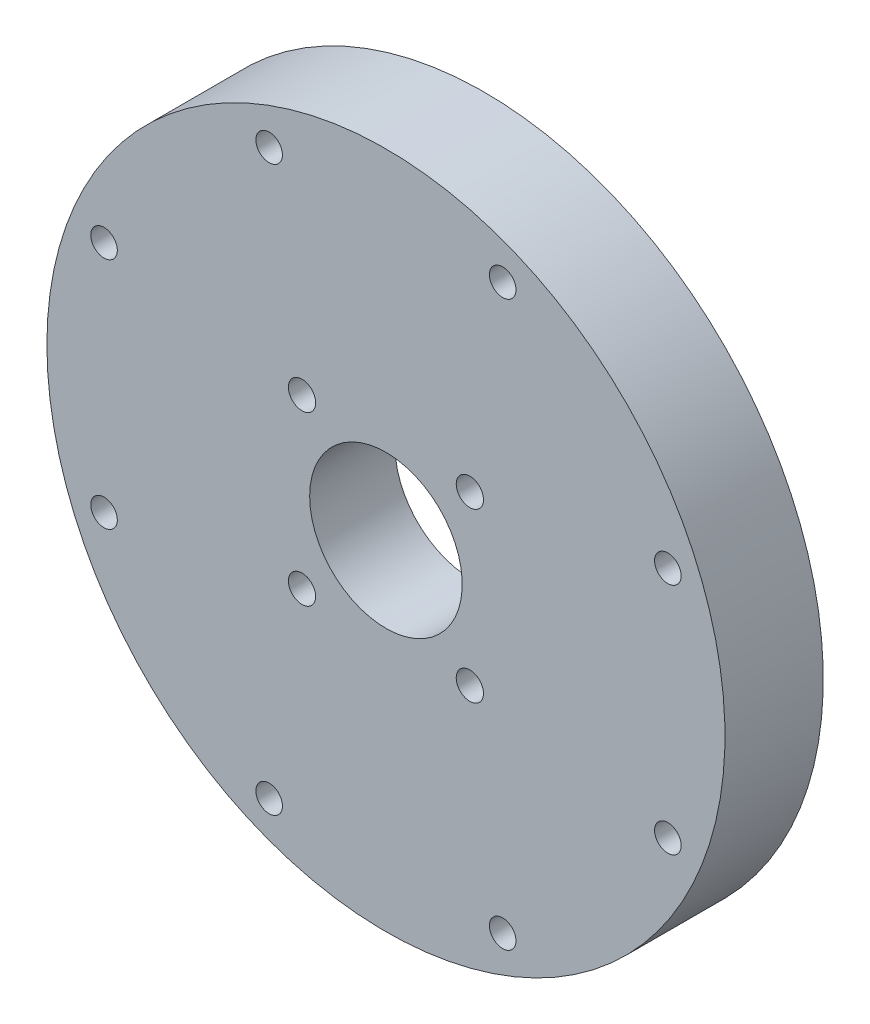
SolidWorks part; units mm, degrees
material "6061-T6 (SS)"
ref_plane "Front Plane" through (0, 0, 0) normal (0, 0, 1) x (1, 0, 0)
ref_plane "Top Plane" through (0, 0, 0) normal (0, 1, 0) x (1, 0, 0)
ref_plane "Right Plane" through (0, 0, 0) normal (1, 0, 0) x (0, 0, -1)
curve "Volute Curve"
  spline degree 3 poles (34.2618, 0, 0) (34.2648, 0.0718, 0) (34.2707, 0.2156, 0) (34.2778, 0.4312, 0) (34.2837, 0.647, 0) (34.2882, 0.8628, 0) (34.2914, 1.0787, 0) (34.2932, 1.2947, 0) (34.2937, 1.5108, 0) (34.2929, 1.7269, 0) (34.2907, 1.9431, 0) (34.2871, 2.1593, 0) (34.2822, 2.3756, 0) (34.2759, 2.5919, 0) (34.2683, 2.8082, 0) (34.2593, 3.0245, 0) (34.2489, 3.2407, 0) (34.2372, 3.457, 0) (34.2242, 3.6733, 0) (34.2098, 3.8895, 0) (34.194, 4.1058, 0) (34.1768, 4.3219, 0) (34.1583, 4.538, 0) (34.1385, 4.7541, 0) (34.1173, 4.9701, 0) (34.0947, 5.186, 0) (34.0708, 5.4018, 0) (34.0454, 5.6175, 0) (34.0188, 5.8331, 0) (33.9908, 6.0486, 0) (33.9614, 6.264, 0) (33.9306, 6.4793, 0) (33.8985, 6.6944, 0) (33.8651, 6.9094, 0) (33.8303, 7.1242, 0) (33.7941, 7.3388, 0) (33.7566, 7.5533, 0) (33.7177, 7.7676, 0) (33.6774, 7.9817, 0) (33.6358, 8.1956, 0) (33.5929, 8.4093, 0) (33.5486, 8.6228, 0) (33.5029, 8.8361, 0) (33.4559, 9.0491, 0) (33.4076, 9.2619, 0) (33.3579, 9.4745, 0) (33.3068, 9.6868, 0) (33.2544, 9.8988, 0) (33.2006, 10.1105, 0) (33.1456, 10.322, 0) (33.0891, 10.5332, 0) (33.0313, 10.744, 0) (32.9722, 10.9546, 0) (32.9118, 11.1648, 0) (32.85, 11.3748, 0) (32.7869, 11.5843, 0) (32.7224, 11.7936, 0) (32.6566, 12.0025, 0) (32.5895, 12.211, 0) (32.521, 12.4192, 0) (32.4513, 12.627, 0) (32.3802, 12.8344, 0) (32.3077, 13.0414, 0) (32.234, 13.248, 0) (32.1589, 13.4542, 0) (32.0826, 13.6599, 0) (32.0049, 13.8653, 0) (31.9259, 14.0702, 0) (31.8456, 14.2747, 0) (31.764, 14.4787, 0) (31.6811, 14.6823, 0) (31.5968, 14.8854, 0) (31.5113, 15.088, 0) (31.4245, 15.2901, 0) (31.3364, 15.4917, 0) (31.247, 15.6929, 0) (31.1563, 15.8935, 0) (31.0644, 16.0936, 0) (30.9711, 16.2932, 0) (30.8766, 16.4922, 0) (30.7808, 16.6907, 0) (30.6837, 16.8886, 0) (30.5854, 17.086, 0) (30.4858, 17.2829, 0) (30.3849, 17.4791, 0) (30.2828, 17.6748, 0) (30.1794, 17.8698, 0) (30.0747, 18.0643, 0) (29.9688, 18.2582, 0) (29.8617, 18.4514, 0) (29.7533, 18.644, 0) (29.6437, 18.836, 0) (29.5328, 19.0274, 0) (29.4208, 19.2181, 0) (29.3074, 19.4081, 0) (29.1929, 19.5975, 0) (29.0771, 19.7862, 0) (28.9601, 19.9742, 0) (28.842, 20.1616, 0) (28.7226, 20.3482, 0) (28.602, 20.5342, 0) (28.4801, 20.7194, 0) (28.3571, 20.904, 0) (28.233, 21.0877, 0) (28.1076, 21.2708, 0) (27.981, 21.4531, 0) (27.8533, 21.6347, 0) (27.7243, 21.8155, 0) (27.5942, 21.9956, 0) (27.463, 22.1748, 0) (27.3306, 22.3533, 0) (27.197, 22.531, 0) (27.0623, 22.708, 0) (26.9264, 22.8841, 0) (26.7894, 23.0594, 0) (26.6512, 23.2339, 0) (26.5119, 23.4075, 0) (26.3715, 23.5804, 0) (26.23, 23.7524, 0) (26.0873, 23.9235, 0) (25.9435, 24.0938, 0) (25.7987, 24.2632, 0) (25.6527, 24.4318, 0) (25.5056, 24.5995, 0) (25.3574, 24.7663, 0) (25.2082, 24.9322, 0) (25.0578, 25.0973, 0) (24.9064, 25.2614, 0) (24.7539, 25.4246, 0) (24.6003, 25.5869, 0) (24.4457, 25.7483, 0) (24.29, 25.9087, 0) (24.1333, 26.0682, 0) (23.9755, 26.2268, 0) (23.8167, 26.3844, 0) (23.6569, 26.541, 0) (23.496, 26.6967, 0) (23.3341, 26.8514, 0) (23.1712, 27.0051, 0) (23.0073, 27.1579, 0) (22.8424, 27.3096, 0) (22.6765, 27.4604, 0) (22.5096, 27.6101, 0) (22.3417, 27.7589, 0) (22.1728, 27.9066, 0) (22.003, 28.0533, 0) (21.8322, 28.199, 0) (21.6604, 28.3436, 0) (21.4877, 28.4872, 0) (21.314, 28.6297, 0) (21.1394, 28.7712, 0) (20.9639, 28.9116, 0) (20.7874, 29.051, 0) (20.61, 29.1892, 0) (20.4317, 29.3264, 0) (20.2524, 29.4626, 0) (20.0723, 29.5976, 0) (19.8913, 29.7315, 0) (19.7094, 29.8643, 0) (19.5266, 29.996, 0) (19.3429, 30.1266, 0) (19.1584, 30.2561, 0) (18.973, 30.3844, 0) (18.7867, 30.5116, 0) (18.5996, 30.6377, 0) (18.4117, 30.7626, 0) (18.2229, 30.8864, 0) (18.0333, 31.009, 0) (17.8429, 31.1304, 0) (17.6516, 31.2507, 0) (17.4596, 31.3698, 0) (17.2667, 31.4878, 0) (17.0731, 31.6045, 0) (16.8786, 31.7201, 0) (16.6834, 31.8344, 0) (16.4875, 31.9476, 0) (16.2907, 32.0596, 0) (16.0932, 32.1703, 0) (15.895, 32.2799, 0) (15.696, 32.3882, 0) (15.4963, 32.4953, 0) (15.2959, 32.6012, 0) (15.0947, 32.7058, 0) (14.8929, 32.8092, 0) (14.6903, 32.9114, 0) (14.487, 33.0123, 0) (14.2831, 33.1119, 0) (14.0784, 33.2103, 0) (13.8731, 33.3075, 0) (13.6672, 33.4033, 0) (13.4606, 33.4979, 0) (13.2533, 33.5912, 0) (13.0454, 33.6833, 0) (12.8368, 33.774, 0) (12.6277, 33.8635, 0) (12.4179, 33.9517, 0) (12.2075, 34.0385, 0) (11.9965, 34.1241, 0) (11.7849, 34.2084, 0) (11.5727, 34.2913, 0) (11.36, 34.373, 0) (11.1467, 34.4533, 0) (10.9328, 34.5323, 0) (10.7183, 34.61, 0) (10.5034, 34.6863, 0) (10.2879, 34.7613, 0) (10.0718, 34.835, 0) (9.8553, 34.9074, 0) (9.6382, 34.9783, 0) (9.4206, 35.048, 0) (9.2025, 35.1163, 0) (8.984, 35.1832, 0) (8.765, 35.2488, 0) (8.5455, 35.313, 0) (8.3255, 35.3759, 0) (8.1051, 35.4374, 0) (7.8842, 35.4975, 0) (7.6629, 35.5562, 0) (7.4412, 35.6136, 0) (7.2191, 35.6696, 0) (6.9965, 35.7242, 0) (6.7736, 35.7774, 0) (6.5503, 35.8292, 0) (6.3265, 35.8796, 0) (6.1024, 35.9287, 0) (5.878, 35.9763, 0) (5.6532, 36.0225, 0) (5.428, 36.0674, 0) (5.2025, 36.1108, 0) (4.9766, 36.1528, 0) (4.7505, 36.1934, 0) (4.524, 36.2326, 0) (4.2972, 36.2704, 0) (4.0701, 36.3067, 0) (3.8428, 36.3417, 0) (3.6151, 36.3752, 0) (3.3872, 36.4073, 0) (3.159, 36.438, 0) (2.9306, 36.4672, 0) (2.7019, 36.495, 0) (2.473, 36.5214, 0) (2.2439, 36.5463, 0) (2.0146, 36.5699, 0) (1.785, 36.5919, 0) (1.5553, 36.6126, 0) (1.3253, 36.6318, 0) (1.0952, 36.6495, 0) (0.8649, 36.6658, 0) (0.6345, 36.6807, 0) (0.4039, 36.6941, 0) (0.1731, 36.706, 0) (-0.0577, 36.7166, 0) (-0.2887, 36.7256, 0) (-0.5199, 36.7332, 0) (-0.7511, 36.7394, 0) (-0.9824, 36.7441, 0) (-1.2138, 36.7474, 0) (-1.4453, 36.7492, 0) (-1.6769, 36.7495, 0) (-1.9085, 36.7484, 0) (-2.1402, 36.7458, 0) (-2.3719, 36.7418, 0) (-2.6037, 36.7363, 0) (-2.8355, 36.7293, 0) (-3.0673, 36.7209, 0) (-3.2991, 36.711, 0) (-3.5309, 36.6997, 0) (-3.7627, 36.6869, 0) (-3.9944, 36.6726, 0) (-4.2262, 36.6569, 0) (-4.4579, 36.6397, 0) (-4.6895, 36.6211, 0) (-4.9211, 36.6009, 0) (-5.1526, 36.5794, 0) (-5.3841, 36.5563, 0) (-5.6154, 36.5318, 0) (-5.8467, 36.5059, 0) (-6.0779, 36.4784, 0) (-6.3089, 36.4495, 0) (-6.5399, 36.4192, 0) (-6.7706, 36.3874, 0) (-7.0013, 36.3541, 0) (-7.2318, 36.3194, 0) (-7.4621, 36.2832, 0) (-7.6923, 36.2455, 0) (-7.9223, 36.2064, 0) (-8.1521, 36.1658, 0) (-8.3817, 36.1238, 0) (-8.6111, 36.0803, 0) (-8.8403, 36.0354, 0) (-9.0693, 35.989, 0) (-9.298, 35.9411, 0) (-9.5265, 35.8918, 0) (-9.7548, 35.8411, 0) (-9.9827, 35.7889, 0) (-10.2105, 35.7352, 0) (-10.4379, 35.6802, 0) (-10.665, 35.6236, 0) (-10.8919, 35.5656, 0) (-11.1184, 35.5062, 0) (-11.3446, 35.4453, 0) (-11.5705, 35.383, 0) (-11.7961, 35.3193, 0) (-12.0213, 35.2541, 0) (-12.2461, 35.1875, 0) (-12.4706, 35.1194, 0) (-12.6948, 35.0499, 0) (-12.9185, 34.979, 0) (-13.1419, 34.9067, 0) (-13.3648, 34.8329, 0) (-13.5874, 34.7578, 0) (-13.8095, 34.6812, 0) (-14.0312, 34.6031, 0) (-14.2525, 34.5237, 0) (-14.4734, 34.4429, 0) (-14.6937, 34.3606, 0) (-14.9137, 34.2769, 0) (-15.1331, 34.1918, 0) (-15.3521, 34.1054, 0) (-15.5706, 34.0175, 0) (-15.7885, 33.9282, 0) (-16.006, 33.8375, 0) (-16.223, 33.7455, 0) (-16.4394, 33.652, 0) (-16.6553, 33.5572, 0) (-16.8707, 33.461, 0) (-17.0855, 33.3634, 0) (-17.2997, 33.2644, 0) (-17.5134, 33.164, 0) (-17.7265, 33.0623, 0) (-17.939, 32.9592, 0) (-18.151, 32.8548, 0) (-18.3623, 32.7489, 0) (-18.573, 32.6418, 0) (-18.7831, 32.5332, 0) (-18.9925, 32.4234, 0) (-19.2014, 32.3121, 0) (-19.4095, 32.1996, 0) (-19.6171, 32.0857, 0) (-19.8239, 31.9704, 0) (-20.0301, 31.8538, 0) (-20.2356, 31.7359, 0) (-20.4404, 31.6167, 0) (-20.6445, 31.4962, 0) (-20.8479, 31.3743, 0) (-21.0506, 31.2511, 0) (-21.2526, 31.1267, 0) (-21.4538, 31.0009, 0) (-21.6543, 30.8738, 0) (-21.854, 30.7454, 0) (-22.053, 30.6158, 0) (-22.2512, 30.4848, 0) (-22.4487, 30.3526, 0) (-22.6453, 30.2191, 0) (-22.8412, 30.0843, 0) (-23.0363, 29.9482, 0) (-23.2305, 29.8109, 0) (-23.424, 29.6723, 0) (-23.6166, 29.5325, 0) (-23.8084, 29.3915, 0) (-23.9994, 29.2491, 0) (-24.1895, 29.1056, 0) (-24.3787, 28.9608, 0) (-24.5671, 28.8148, 0) (-24.7546, 28.6676, 0) (-24.9413, 28.5191, 0) (-25.127, 28.3694, 0) (-25.3119, 28.2186, 0) (-25.4958, 28.0665, 0) (-25.6789, 27.9132, 0) (-25.861, 27.7587, 0) (-26.0422, 27.6031, 0) (-26.2224, 27.4463, 0) (-26.4018, 27.2882, 0) (-26.5801, 27.1291, 0) (-26.7576, 26.9687, 0) (-26.934, 26.8072, 0) (-27.1095, 26.6446, 0) (-27.284, 26.4808, 0) (-27.4575, 26.3159, 0) (-27.63, 26.1498, 0) (-27.8015, 25.9826, 0) (-27.972, 25.8143, 0) (-28.1415, 25.6448, 0) (-28.31, 25.4743, 0) (-28.4774, 25.3027, 0) (-28.6438, 25.1299, 0) (-28.8092, 24.9561, 0) (-28.9735, 24.7811, 0) (-29.1367, 24.6051, 0) (-29.2989, 24.4281, 0) (-29.46, 24.2499, 0) (-29.62, 24.0707, 0) (-29.7789, 23.8905, 0) (-29.9368, 23.7092, 0) (-30.0935, 23.5268, 0) (-30.2491, 23.3435, 0) (-30.4036, 23.1591, 0) (-30.557, 22.9737, 0) (-30.7093, 22.7872, 0) (-30.8604, 22.5998, 0) (-31.0104, 22.4114, 0) (-31.1592, 22.2219, 0) (-31.3069, 22.0315, 0) (-31.4534, 21.8402, 0) (-31.5988, 21.6478, 0) (-31.7429, 21.4545, 0) (-31.8859, 21.2602, 0) (-32.0277, 21.065, 0) (-32.1684, 20.8688, 0) (-32.3078, 20.6717, 0) (-32.446, 20.4737, 0) (-32.583, 20.2747, 0) (-32.7188, 20.0748, 0) (-32.8533, 19.8741, 0) (-32.9866, 19.6724, 0) (-33.1187, 19.4698, 0) (-33.2496, 19.2664, 0) (-33.3792, 19.0621, 0) (-33.5075, 18.8569, 0) (-33.6346, 18.6509, 0) (-33.7604, 18.444, 0) (-33.885, 18.2362, 0) (-34.0082, 18.0276, 0) (-34.1302, 17.8182, 0) (-34.2509, 17.608, 0) (-34.3703, 17.397, 0) (-34.4884, 17.1851, 0) (-34.6052, 16.9725, 0) (-34.7207, 16.7591, 0) (-34.8349, 16.5449, 0) (-34.9478, 16.3299, 0) (-35.0593, 16.1141, 0) (-35.1695, 15.8976, 0) (-35.2784, 15.6804, 0) (-35.3859, 15.4624, 0) (-35.4921, 15.2436, 0) (-35.597, 15.0242, 0) (-35.7004, 14.804, 0) (-35.8026, 14.5832, 0) (-35.9033, 14.3616, 0) (-36.0027, 14.1393, 0) (-36.1007, 13.9164, 0) (-36.1973, 13.6928, 0) (-36.2926, 13.4685, 0) (-36.3864, 13.2436, 0) (-36.4789, 13.018, 0) (-36.57, 12.7918, 0) (-36.6596, 12.5649, 0) (-36.7479, 12.3374, 0) (-36.8348, 12.1094, 0) (-36.9202, 11.8807, 0) (-37.0042, 11.6514, 0) (-37.0868, 11.4215, 0) (-37.168, 11.1911, 0) (-37.2477, 10.96, 0) (-37.326, 10.7285, 0) (-37.4029, 10.4963, 0) (-37.4783, 10.2637, 0) (-37.5523, 10.0305, 0) (-37.6248, 9.7967, 0) (-37.6959, 9.5625, 0) (-37.7655, 9.3277, 0) (-37.8337, 9.0925, 0) (-37.9004, 8.8568, 0) (-37.9656, 8.6205, 0) (-38.0293, 8.3839, 0) (-38.0916, 8.1467, 0) (-38.1524, 7.9091, 0) (-38.2117, 7.6711, 0) (-38.2696, 7.4326, 0) (-38.3259, 7.1937, 0) (-38.3808, 6.9544, 0) (-38.4342, 6.7147, 0) (-38.486, 6.4746, 0) (-38.5364, 6.2341, 0) (-38.5853, 5.9932, 0) (-38.6326, 5.7519, 0) (-38.6785, 5.5103, 0) (-38.7229, 5.2684, 0) (-38.7657, 5.0261, 0) (-38.807, 4.7835, 0) (-38.8468, 4.5405, 0) (-38.8851, 4.2973, 0) (-38.9219, 4.0537, 0) (-38.9571, 3.8099, 0) (-38.9908, 3.5657, 0) (-39.023, 3.3213, 0) (-39.0537, 3.0767, 0) (-39.0828, 2.8317, 0) (-39.1104, 2.5866, 0) (-39.1364, 2.3412, 0) (-39.1609, 2.0955, 0) (-39.1839, 1.8497, 0) (-39.2053, 1.6037, 0) (-39.2252, 1.3574, 0) (-39.2435, 1.111, 0) (-39.2603, 0.8644, 0) (-39.2756, 0.6176, 0) (-39.2893, 0.3707, 0) (-39.3014, 0.1236, 0) (-39.312, -0.1236, 0) (-39.321, -0.371, 0) (-39.3285, -0.6185, 0) (-39.3344, -0.866, 0) (-39.3388, -1.1137, 0) (-39.3416, -1.3615, 0) (-39.3428, -1.6093, 0) (-39.3425, -1.8572, 0) (-39.3406, -2.1052, 0) (-39.3372, -2.3532, 0) (-39.3322, -2.6013, 0) (-39.3257, -2.8494, 0) (-39.3175, -3.0975, 0) (-39.3078, -3.3456, 0) (-39.2966, -3.5937, 0) (-39.2838, -3.8418, 0) (-39.2694, -4.0899, 0) (-39.2534, -4.338, 0) (-39.2359, -4.586, 0) (-39.2168, -4.834, 0) (-39.1962, -5.0819, 0) (-39.174, -5.3298, 0) (-39.1502, -5.5776, 0) (-39.1248, -5.8252, 0) (-39.0979, -6.0728, 0) (-39.0694, -6.3203, 0) (-39.0394, -6.5677, 0) (-39.0078, -6.8149, 0) (-38.9746, -7.062, 0) (-38.9399, -7.309, 0) (-38.9036, -7.5558, 0) (-38.8657, -7.8024, 0) (-38.8263, -8.0488, 0) (-38.7853, -8.2951, 0) (-38.7427, -8.5411, 0) (-38.6986, -8.787, 0) (-38.653, -9.0326, 0) (-38.6057, -9.2781, 0) (-38.557, -9.5232, 0) (-38.5066, -9.7682, 0) (-38.4547, -10.0128, 0) (-38.4013, -10.2572, 0) (-38.3463, -10.5014, 0) (-38.2897, -10.7452, 0) (-38.2316, -10.9888, 0) (-38.172, -11.232, 0) (-38.1108, -11.475, 0) (-38.048, -11.7176, 0) (-37.9838, -11.9598, 0) (-37.9179, -12.2018, 0) (-37.8506, -12.4433, 0) (-37.7817, -12.6845, 0) (-37.7112, -12.9254, 0) (-37.6393, -13.1658, 0) (-37.5658, -13.4059, 0) (-37.4907, -13.6455, 0) (-37.4142, -13.8848, 0) (-37.3361, -14.1236, 0) (-37.2565, -14.362, 0) (-37.1753, -14.5999, 0) (-37.0927, -14.8374, 0) (-37.0085, -15.0744, 0) (-36.9228, -15.311, 0) (-36.8357, -15.547, 0) (-36.747, -15.7826, 0) (-36.6568, -16.0177, 0) (-36.5651, -16.2523, 0) (-36.4719, -16.4863, 0) (-36.3772, -16.7199, 0) (-36.281, -16.9528, 0) (-36.1833, -17.1853, 0) (-36.0841, -17.4172, 0) (-35.9834, -17.6485, 0) (-35.8813, -17.8792, 0) (-35.7777, -18.1094, 0) (-35.6726, -18.3389, 0) (-35.566, -18.5679, 0) (-35.458, -18.7962, 0) (-35.3485, -19.0239, 0) (-35.2376, -19.251, 0) (-35.1251, -19.4774, 0) (-35.0113, -19.7032, 0) (-34.896, -19.9283, 0) (-34.7792, -20.1528, 0) (-34.661, -20.3765, 0) (-34.5414, -20.5996, 0) (-34.4203, -20.822, 0) (-34.2978, -21.0437, 0) (-34.1738, -21.2646, 0) (-34.0485, -21.4849, 0) (-33.9217, -21.7044, 0) (-33.7935, -21.9231, 0) (-33.6639, -22.1411, 0) (-33.5329, -22.3584, 0) (-33.4005, -22.5748, 0) (-33.2667, -22.7905, 0) (-33.1315, -23.0054, 0) (-32.995, -23.2195, 0) (-32.857, -23.4328, 0) (-32.7177, -23.6453, 0) (-32.577, -23.8569, 0) (-32.4349, -24.0677, 0) (-32.2915, -24.2777, 0) (-32.1467, -24.4868, 0) (-32.0006, -24.6951, 0) (-31.8531, -24.9025, 0) (-31.7042, -25.109, 0) (-31.5541, -25.3146, 0) (-31.4026, -25.5194, 0) (-31.2497, -25.7232, 0) (-31.0956, -25.9261, 0) (-30.9401, -26.1281, 0) (-30.7833, -26.3292, 0) (-30.6253, -26.5293, 0) (-30.4659, -26.7285, 0) (-30.3052, -26.9267, 0) (-30.1433, -27.124, 0) (-29.98, -27.3203, 0) (-29.8155, -27.5156, 0) (-29.6497, -27.7099, 0) (-29.4827, -27.9032, 0) (-29.3144, -28.0956, 0) (-29.1448, -28.2869, 0) (-28.974, -28.4772, 0) (-28.8019, -28.6664, 0) (-28.6287, -28.8546, 0) (-28.4542, -29.0418, 0) (-28.2784, -29.2279, 0) (-28.1015, -29.413, 0) (-27.9233, -29.597, 0) (-27.744, -29.7799, 0) (-27.5634, -29.9618, 0) (-27.3817, -30.1425, 0) (-27.1987, -30.3221, 0) (-27.0146, -30.5007, 0) (-26.8294, -30.6781, 0) (-26.6429, -30.8544, 0) (-26.4554, -31.0296, 0) (-26.2666, -31.2036, 0) (-26.0767, -31.3765, 0) (-25.8857, -31.5482, 0) (-25.6936, -31.7188, 0) (-25.5003, -31.8882, 0) (-25.306, -32.0564, 0) (-25.1105, -32.2234, 0) (-24.9139, -32.3893, 0) (-24.7162, -32.5539, 0) (-24.5175, -32.7174, 0) (-24.3176, -32.8796, 0) (-24.1167, -33.0406, 0) (-23.9147, -33.2004, 0) (-23.7117, -33.359, 0) (-23.5076, -33.5163, 0) (-23.3025, -33.6724, 0) (-23.0964, -33.8272, 0) (-22.8892, -33.9807, 0) (-22.681, -34.133, 0) (-22.4718, -34.2841, 0) (-22.2616, -34.4338, 0) (-22.0504, -34.5822, 0) (-21.8382, -34.7294, 0) (-21.6251, -34.8752, 0) (-21.4109, -35.0198, 0) (-21.1959, -35.163, 0) (-20.9798, -35.3049, 0) (-20.7628, -35.4455, 0) (-20.5449, -35.5848, 0) (-20.326, -35.7227, 0) (-20.1062, -35.8593, 0) (-19.8855, -35.9945, 0) (-19.6639, -36.1284, 0) (-19.4414, -36.2609, 0) (-19.2181, -36.392, 0) (-18.9938, -36.5218, 0) (-18.7686, -36.6502, 0) (-18.5426, -36.7772, 0) (-18.3158, -36.9028, 0) (-18.0881, -37.027, 0) (-17.8595, -37.1498, 0) (-17.6302, -37.2712, 0) (-17.4, -37.3911, 0) (-17.169, -37.5097, 0) (-16.9372, -37.6268, 0) (-16.7046, -37.7425, 0) (-16.4712, -37.8568, 0) (-16.237, -37.9696, 0) (-16.0021, -38.081, 0) (-15.7664, -38.1909, 0) (-15.53, -38.2994, 0) (-15.2928, -38.4064, 0) (-15.0549, -38.5119, 0) (-14.8163, -38.616, 0) (-14.577, -38.7185, 0) (-14.3369, -38.8196, 0) (-14.0962, -38.9192, 0) (-13.8547, -39.0174, 0) (-13.6126, -39.114, 0) (-13.3699, -39.2091, 0) (-13.1265, -39.3027, 0) (-12.8824, -39.3949, 0) (-12.6377, -39.4854, 0) (-12.3923, -39.5745, 0) (-12.1464, -39.6621, 0) (-11.8998, -39.7481, 0) (-11.6526, -39.8326, 0) (-11.4048, -39.9155, 0) (-11.1565, -39.997, 0) (-10.9076, -40.0768, 0) (-10.6581, -40.1552, 0) (-10.408, -40.2319, 0) (-10.1575, -40.3071, 0) (-9.9063, -40.3808, 0) (-9.6547, -40.4529, 0) (-9.4025, -40.5234, 0) (-9.1499, -40.5924, 0) (-8.8967, -40.6598, 0) (-8.6431, -40.7256, 0) (-8.389, -40.7898, 0) (-8.1344, -40.8524, 0) (-7.8793, -40.9135, 0) (-7.6239, -40.9729, 0) (-7.3679, -41.0308, 0) (-7.1116, -41.087, 0) (-6.8548, -41.1417, 0) (-6.5977, -41.1948, 0) (-6.3401, -41.2462, 0) (-6.0821, -41.2961, 0) (-5.8238, -41.3443, 0) (-5.5651, -41.3909, 0) (-5.3061, -41.4359, 0) (-5.0467, -41.4793, 0) (-4.7869, -41.5211, 0) (-4.5269, -41.5612, 0) (-4.2665, -41.5997, 0) (-4.0058, -41.6366, 0) (-3.7449, -41.6718, 0) (-3.4836, -41.7054, 0) (-3.2221, -41.7374, 0) (-2.9603, -41.7677, 0) (-2.6982, -41.7964, 0) (-2.4359, -41.8234, 0) (-2.1734, -41.8488, 0) (-1.9106, -41.8726, 0) (-1.6477, -41.8947, 0) (-1.3845, -41.9151, 0) (-1.1212, -41.9339, 0) (-0.8576, -41.9511, 0) (-0.5939, -41.9666, 0) (-0.33, -41.9804, 0) (-0.066, -41.9926, 0) (0.1981, -42.0031, 0) (0.4624, -42.012, 0) (0.7268, -42.0192, 0) (0.9914, -42.0247, 0) (1.256, -42.0286, 0) (1.5207, -42.0308, 0) (1.7855, -42.0313, 0) (2.0503, -42.0302, 0) (2.3152, -42.0274, 0) (2.5802, -42.0229, 0) (2.8452, -42.0168, 0) (3.1102, -42.0089, 0) (3.3752, -41.9995, 0) (3.6403, -41.9883, 0) (3.9053, -41.9755, 0) (4.1703, -41.961, 0) (4.4353, -41.9448, 0) (4.7002, -41.927, 0) (4.9651, -41.9075, 0) (5.2299, -41.8863, 0) (5.4947, -41.8634, 0) (5.7594, -41.8389, 0) (6.024, -41.8127, 0) (6.2885, -41.7848, 0) (6.5528, -41.7553, 0) (6.8171, -41.7241, 0) (7.0812, -41.6912, 0) (7.3452, -41.6566, 0) (7.609, -41.6204, 0) (7.8727, -41.5825, 0) (8.1362, -41.5429, 0) (8.3995, -41.5017, 0) (8.6626, -41.4588, 0) (8.9254, -41.4142, 0) (9.1881, -41.3679, 0) (9.4506, -41.32, 0) (9.7128, -41.2705, 0) (9.9747, -41.2192, 0) (10.2364, -41.1663, 0) (10.4979, -41.1118, 0) (10.759, -41.0556, 0) (11.0199, -40.9977, 0) (11.2804, -40.9382, 0) (11.5407, -40.877, 0) (11.8006, -40.8141, 0) (12.0602, -40.7496, 0) (12.3194, -40.6835, 0) (12.5783, -40.6157, 0) (12.8368, -40.5463, 0) (13.0949, -40.4752, 0) (13.3527, -40.4025, 0) (13.6101, -40.3281, 0) (13.867, -40.2521, 0) (14.1235, -40.1745, 0) (14.3797, -40.0952, 0) (14.6353, -40.0143, 0) (14.8905, -39.9318, 0) (15.1453, -39.8476, 0) (15.3996, -39.7618, 0) (15.6534, -39.6744, 0) (15.9067, -39.5854, 0) (16.1596, -39.4948, 0) (16.4119, -39.4025, 0) (16.6637, -39.3087, 0) (16.9149, -39.2132, 0) (17.1657, -39.1161, 0) (17.4158, -39.0174, 0) (17.6654, -38.9172, 0) (17.9145, -38.8153, 0) (18.1629, -38.7118, 0) (18.4108, -38.6068, 0) (18.658, -38.5001, 0) (18.9047, -38.3919, 0) (19.1507, -38.2821, 0) (19.3961, -38.1707, 0) (19.6408, -38.0578, 0) (19.8849, -37.9433, 0) (20.1283, -37.8272, 0) (20.3711, -37.7095, 0) (20.6132, -37.5904, 0) (20.8546, -37.4696, 0) (21.0952, -37.3473, 0) (21.3352, -37.2235, 0) (21.5744, -37.0981, 0) (21.8129, -36.9712, 0) (22.0507, -36.8427, 0) (22.2877, -36.7127, 0) (22.524, -36.5812, 0) (22.7594, -36.4482, 0) (22.9941, -36.3137, 0) (23.228, -36.1776, 0) (23.4611, -36.0401, 0) (23.6934, -35.901, 0) (23.9249, -35.7605, 0) (24.1556, -35.6184, 0) (24.3854, -35.4749, 0) (24.6143, -35.3299, 0) (24.8424, -35.1834, 0) (25.0696, -35.0355, 0) (25.296, -34.8861, 0) (25.5214, -34.7352, 0) (25.746, -34.5828, 0) (25.9696, -34.4291, 0) (26.1924, -34.2738, 0) (26.4142, -34.1172, 0) (26.6351, -33.9591, 0) (26.855, -33.7995, 0) (27.074, -33.6386, 0) (27.292, -33.4762, 0) (27.5091, -33.3124, 0) (27.7252, -33.1472, 0) (27.9402, -32.9807, 0) (28.1543, -32.8127, 0) (28.3674, -32.6433, 0) (28.5795, -32.4726, 0) (28.7905, -32.3004, 0) (29.0005, -32.127, 0) (29.2095, -31.9521, 0) (29.4174, -31.7759, 0) (29.6242, -31.5983, 0) (29.83, -31.4194, 0) (30.0347, -31.2392, 0) (30.2383, -31.0576, 0) (30.4408, -30.8747, 0) (30.6422, -30.6905, 0) (30.8426, -30.5049, 0) (31.0417, -30.3181, 0) (31.2398, -30.1299, 0) (31.4367, -29.9405, 0) (31.6325, -29.7498, 0) (31.8271, -29.5578, 0) (32.0205, -29.3645, 0) (32.2128, -29.17, 0) (32.4039, -28.9742, 0) (32.5938, -28.7772, 0) (32.7825, -28.5789, 0) (32.97, -28.3794, 0) (33.1563, -28.1787, 0) (33.3414, -27.9767, 0) (33.5252, -27.7736, 0) (33.7079, -27.5692, 0) (33.8892, -27.3636, 0) (34.0693, -27.1569, 0) (34.2482, -26.9489, 0) (34.4258, -26.7398, 0) (34.6021, -26.5295, 0) (34.7771, -26.3181, 0) (34.9509, -26.1055, 0) (35.1233, -25.8917, 0) (35.2944, -25.6768, 0) (35.4643, -25.4608, 0) (35.6328, -25.2437, 0) (35.7999, -25.0255, 0) (35.9658, -24.8061, 0) (36.1303, -24.5857, 0) (36.2934, -24.3641, 0) (36.4552, -24.1415, 0) (36.6157, -23.9179, 0) (36.7747, -23.6931, 0) (36.9324, -23.4673, 0) (37.0887, -23.2405, 0) (37.2436, -23.0126, 0) (37.3971, -22.7837, 0) (37.5492, -22.5538, 0) (37.6999, -22.3228, 0) (37.8491, -22.0909, 0) (37.997, -21.858, 0) (38.1434, -21.624, 0) (38.2884, -21.3891, 0) (38.4319, -21.1533, 0) (38.574, -20.9165, 0) (38.7146, -20.6787, 0) (38.8537, -20.44, 0) (38.9914, -20.2003, 0) (39.1276, -19.9598, 0) (39.2623, -19.7183, 0) (39.3956, -19.4759, 0) (39.5273, -19.2326, 0) (39.6575, -18.9884, 0) (39.7863, -18.7434, 0) (39.9135, -18.4975, 0) (40.0392, -18.2507, 0) (40.1633, -18.0031, 0) (40.286, -17.7546, 0) (40.4071, -17.5053, 0) (40.5267, -17.2552, 0) (40.6447, -17.0043, 0) (40.7611, -16.7525, 0) (40.876, -16.5, 0) (40.9894, -16.2467, 0) (41.1012, -15.9927, 0) (41.2114, -15.7378, 0) (41.32, -15.4822, 0) (41.427, -15.2259, 0) (41.5325, -14.9688, 0) (41.6363, -14.711, 0) (41.7386, -14.4525, 0) (41.8392, -14.1933, 0) (41.9383, -13.9334, 0) (42.0357, -13.6728, 0) (42.1315, -13.4116, 0) (42.2257, -13.1496, 0) (42.3182, -12.8871, 0) (42.4092, -12.6238, 0) (42.4985, -12.36, 0) (42.5861, -12.0955, 0) (42.6721, -11.8304, 0) (42.7565, -11.5647, 0) (42.8392, -11.2984, 0) (42.9202, -11.0315, 0) (42.9996, -10.7641, 0) (43.0773, -10.4961, 0) (43.1534, -10.2275, 0) (43.2277, -9.9584, 0) (43.3004, -9.6888, 0) (43.3715, -9.4186, 0) (43.4408, -9.148, 0) (43.5084, -8.8768, 0) (43.5744, -8.6052, 0) (43.6386, -8.333, 0) (43.7012, -8.0604, 0) (43.7621, -7.7874, 0) (43.8212, -7.5139, 0) (43.8786, -7.24, 0) (43.9344, -6.9656, 0) (43.9884, -6.6908, 0) (44.0407, -6.4156, 0) (44.0913, -6.1401, 0) (44.1401, -5.8641, 0) (44.1872, -5.5878, 0) (44.2326, -5.3111, 0) (44.2763, -5.0341, 0) (44.3182, -4.7567, 0) (44.3584, -4.479, 0) (44.3969, -4.201, 0) (44.4336, -3.9226, 0) (44.4686, -3.644, 0) (44.5018, -3.3651, 0) (44.5333, -3.0859, 0) (44.563, -2.8065, 0) (44.591, -2.5268, 0) (44.6172, -2.2468, 0) (44.6416, -1.9667, 0) (44.6643, -1.6863, 0) (44.6853, -1.4057, 0) (44.7044, -1.1249, 0) (44.7219, -0.8439, 0) (44.7375, -0.5628, 0) (44.7515, -0.2815, 0) (44.7593, -0.0938, 0) (44.7632, 0, 0) knots 0 0 0 0 0.000871 0.001743 0.002614 0.003486 0.004358 0.005231 0.006103 0.006976 0.007849 0.008723 0.009596 0.01047 0.011344 0.012219 0.013093 0.013968 0.014843 0.015718 0.016594 0.017469 0.018345 0.019222 0.020098 0.020975 0.021852 0.022729 0.023606 0.024484 0.025362 0.02624 0.027119 0.027997 0.028876 0.029755 0.030635 0.031514 0.032394 0.033274 0.034154 0.035035 0.035916 0.036797 0.037678 0.03856 0.039442 0.040324 0.041206 0.042089 0.042971 0.043854 0.044738 0.045621 0.046505 0.047389 0.048273 0.049158 0.050042 0.050927 0.051813 0.052698 0.053584 0.05447 0.055356 0.056242 0.057129 0.058016 0.058903 0.059791 0.060678 0.061566 0.062454 0.063343 0.064232 0.06512 0.06601 0.066899 0.067789 0.068679 0.069569 0.070459 0.07135 0.072241 0.073132 0.074023 0.074915 0.075807 0.076699 0.077591 0.078484 0.079377 0.08027 0.081163 0.082057 0.082951 0.083845 0.084739 0.085634 0.086529 0.087424 0.088319 0.089215 0.090111 0.091007 0.091903 0.0928 0.093696 0.094594 0.095491 0.096388 0.097286 0.098184 0.099083 0.099981 0.10088 0.101779 0.102679 0.103578 0.104478 0.105378 0.106279 0.107179 0.10808 0.108981 0.109882 0.110784 0.111686 0.112588 0.11349 0.114393 0.115296 0.116199 0.117102 0.118006 0.11891 0.119814 0.120718 0.121623 0.122528 0.123433 0.124338 0.125244 0.12615 0.127056 0.127962 0.128869 0.129776 0.130683 0.13159 0.132498 0.133406 0.134314 0.135222 0.136131 0.13704 0.137949 0.138858 0.139768 0.140678 0.141588 0.142498 0.143409 0.14432 0.145231 0.146142 0.147054 0.147966 0.148878 0.149791 0.150703 0.151616 0.152529 0.153443 0.154357 0.155271 0.156185 0.157099 0.158014 0.158929 0.159844 0.16076 0.161675 0.162591 0.163508 0.164424 0.165341 0.166258 0.167175 0.168093 0.16901 0.169928 0.170847 0.171765 0.172684 0.173603 0.174522 0.175442 0.176362 0.177282 0.178202 0.179123 0.180044 0.180965 0.181886 0.182808 0.183729 0.184652 0.185574 0.186497 0.187419 0.188343 0.189266 0.19019 0.191113 0.192038 0.192962 0.193887 0.194812 0.195737 0.196662 0.197588 0.198514 0.19944 0.200367 0.201293 0.20222 0.203147 0.204075 0.205003 0.205931 0.206859 0.207787 0.208716 0.209645 0.210575 0.211504 0.212434 0.213364 0.214294 0.215225 0.216156 0.217087 0.218018 0.21895 0.219882 0.220814 0.221746 0.222679 0.223612 0.224545 0.225478 0.226412 0.227346 0.22828 0.229214 0.230149 0.231084 0.232019 0.232955 0.23389 0.234826 0.235763 0.236699 0.237636 0.238573 0.23951 0.240448 0.241386 0.242324 0.243262 0.244201 0.245139 0.246078 0.247018 0.247957 0.248897 0.249837 0.250778 0.251718 0.252659 0.253601 0.254542 0.255484 0.256426 0.257368 0.25831 0.259253 0.260196 0.261139 0.262083 0.263027 0.263971 0.264915 0.265859 0.266804 0.267749 0.268695 0.26964 0.270586 0.271532 0.272479 0.273425 0.274372 0.275319 0.276267 0.277214 0.278162 0.27911 0.280059 0.281008 0.281957 0.282906 0.283855 0.284805 0.285755 0.286705 0.287656 0.288607 0.289558 0.290509 0.291461 0.292413 0.293365 0.294317 0.29527 0.296223 0.297176 0.298129 0.299083 0.300037 0.300991 0.301946 0.3029 0.303855 0.30481 0.305766 0.306722 0.307678 0.308634 0.309591 0.310548 0.311505 0.312462 0.31342 0.314377 0.315336 0.316294 0.317253 0.318212 0.319171 0.32013 0.32109 0.32205 0.32301 0.323971 0.324931 0.325892 0.326854 0.327815 0.328777 0.329739 0.330702 0.331664 0.332627 0.33359 0.334554 0.335517 0.336481 0.337445 0.33841 0.339375 0.34034 0.341305 0.34227 0.343236 0.344202 0.345168 0.346135 0.347102 0.348069 0.349036 0.350004 0.350972 0.35194 0.352908 0.353877 0.354846 0.355815 0.356785 0.357754 0.358724 0.359695 0.360665 0.361636 0.362607 0.363578 0.36455 0.365522 0.366494 0.367466 0.368439 0.369412 0.370385 0.371358 0.372332 0.373306 0.37428 0.375255 0.37623 0.377205 0.37818 0.379156 0.380131 0.381107 0.382084 0.38306 0.384037 0.385015 0.385992 0.38697 0.387948 0.388926 0.389904 0.390883 0.391862 0.392841 0.393821 0.394801 0.395781 0.396761 0.397742 0.398723 0.399704 0.400685 0.401667 0.402649 0.403631 0.404614 0.405596 0.406579 0.407563 0.408546 0.40953 0.410514 0.411498 0.412483 0.413468 0.414453 0.415438 0.416424 0.41741 0.418396 0.419383 0.420369 0.421357 0.422344 0.423331 0.424319 0.425307 0.426296 0.427284 0.428273 0.429262 0.430252 0.431241 0.432231 0.433222 0.434212 0.435203 0.436194 0.437185 0.438177 0.439169 0.440161 0.441153 0.442146 0.443139 0.444132 0.445125 0.446119 0.447113 0.448107 0.449102 0.450096 0.451091 0.452087 0.453082 0.454078 0.455074 0.456071 0.457067 0.458064 0.459061 0.460059 0.461057 0.462055 0.463053 0.464051 0.46505 0.466049 0.467049 0.468048 0.469048 0.470048 0.471049 0.472049 0.47305 0.474052 0.475053 0.476055 0.477057 0.478059 0.479062 0.480065 0.481068 0.482071 0.483075 0.484079 0.485083 0.486087 0.487092 0.488097 0.489102 0.490108 0.491114 0.49212 0.493126 0.494133 0.49514 0.496147 0.497154 0.498162 0.49917 0.500178 0.501187 0.502196 0.503205 0.504214 0.505224 0.506233 0.507244 0.508254 0.509265 0.510276 0.511287 0.512298 0.51331 0.514322 0.515334 0.516347 0.51736 0.518373 0.519386 0.5204 0.521414 0.522428 0.523442 0.524457 0.525472 0.526488 0.527503 0.528519 0.529535 0.530551 0.531568 0.532585 0.533602 0.53462 0.535637 0.536655 0.537673 0.538692 0.539711 0.54073 0.541749 0.542769 0.543789 0.544809 0.545829 0.54685 0.547871 0.548892 0.549914 0.550936 0.551958 0.55298 0.554003 0.555026 0.556049 0.557072 0.558096 0.55912 0.560144 0.561169 0.562193 0.563218 0.564244 0.565269 0.566295 0.567321 0.568348 0.569375 0.570402 0.571429 0.572456 0.573484 0.574512 0.575541 0.576569 0.577598 0.578627 0.579657 0.580686 0.581716 0.582747 0.583777 0.584808 0.585839 0.58687 0.587902 0.588934 0.589966 0.590998 0.592031 0.593064 0.594097 0.595131 0.596165 0.597199 0.598233 0.599268 0.600303 0.601338 0.602373 0.603409 0.604445 0.605481 0.606518 0.607554 0.608592 0.609629 0.610667 0.611704 0.612743 0.613781 0.61482 0.615859 0.616898 0.617938 0.618977 0.620018 0.621058 0.622099 0.62314 0.624181 0.625222 0.626264 0.627306 0.628348 0.629391 0.630434 0.631477 0.63252 0.633564 0.634608 0.635652 0.636697 0.637741 0.638786 0.639832 0.640877 0.641923 0.642969 0.644016 0.645062 0.646109 0.647157 0.648204 0.649252 0.6503 0.651348 0.652397 0.653446 0.654495 0.655545 0.656594 0.657644 0.658695 0.659745 0.660796 0.661847 0.662898 0.66395 0.665002 0.666054 0.667107 0.668159 0.669212 0.670266 0.671319 0.672373 0.673427 0.674482 0.675536 0.676591 0.677647 0.678702 0.679758 0.680814 0.68187 0.682927 0.683984 0.685041 0.686099 0.687156 0.688214 0.689273 0.690331 0.69139 0.692449 0.693508 0.694568 0.695628 0.696688 0.697749 0.69881 0.699871 0.700932 0.701994 0.703055 0.704118 0.70518 0.706243 0.707306 0.708369 0.709433 0.710496 0.71156 0.712625 0.713689 0.714754 0.71582 0.716885 0.717951 0.719017 0.720083 0.72115 0.722217 0.723284 0.724351 0.725419 0.726487 0.727555 0.728624 0.729693 0.730762 0.731831 0.732901 0.733971 0.735041 0.736111 0.737182 0.738253 0.739324 0.740396 0.741468 0.74254 0.743612 0.744685 0.745758 0.746831 0.747905 0.748979 0.750053 0.751127 0.752202 0.753277 0.754352 0.755428 0.756503 0.757579 0.758656 0.759732 0.760809 0.761886 0.762964 0.764041 0.765119 0.766198 0.767276 0.768355 0.769434 0.770514 0.771593 0.772673 0.773754 0.774834 0.775915 0.776996 0.778077 0.779159 0.780241 0.781323 0.782405 0.783488 0.784571 0.785654 0.786738 0.787822 0.788906 0.789991 0.791075 0.79216 0.793245 0.794331 0.795417 0.796503 0.797589 0.798676 0.799763 0.80085 0.801938 0.803025 0.804113 0.805202 0.80629 0.807379 0.808468 0.809558 0.810648 0.811738 0.812828 0.813919 0.815009 0.816101 0.817192 0.818284 0.819376 0.820468 0.82156 0.822653 0.823746 0.82484 0.825933 0.827027 0.828122 0.829216 0.830311 0.831406 0.832501 0.833597 0.834693 0.835789 0.836885 0.837982 0.839079 0.840177 0.841274 0.842372 0.84347 0.844569 0.845667 0.846766 0.847866 0.848965 0.850065 0.851165 0.852266 0.853366 0.854467 0.855568 0.85667 0.857772 0.858874 0.859976 0.861079 0.862182 0.863285 0.864389 0.865492 0.866596 0.867701 0.868805 0.86991 0.871016 0.872121 0.873227 0.874333 0.875439 0.876546 0.877653 0.87876 0.879867 0.880975 0.882083 0.883191 0.8843 0.885409 0.886518 0.887627 0.888737 0.889847 0.890957 0.892068 0.893179 0.89429 0.895401 0.896513 0.897625 0.898737 0.89985 0.900962 0.902075 0.903189 0.904303 0.905416 0.906531 0.907645 0.90876 0.909875 0.91099 0.912106 0.913222 0.914338 0.915455 0.916571 0.917689 0.918806 0.919923 0.921041 0.92216 0.923278 0.924397 0.925516 0.926635 0.927755 0.928875 0.929995 0.931115 0.932236 0.933357 0.934478 0.9356 0.936722 0.937844 0.938966 0.940089 0.941212 0.942335 0.943459 0.944583 0.945707 0.946831 0.947956 0.949081 0.950206 0.951332 0.952458 0.953584 0.95471 0.955837 0.956964 0.958091 0.959219 0.960347 0.961475 0.962603 0.963732 0.964861 0.96599 0.96712 0.968249 0.96938 0.97051 0.971641 0.972772 0.973903 0.975034 0.976166 0.977298 0.978431 0.979563 0.980696 0.981829 0.982963 0.984097 0.985231 0.986365 0.9875 0.988635 0.98977 0.990906 0.992041 0.993178 0.994314 0.995451 0.996587 0.997725 0.998862 1 1 1 1
sketch "Sketch16" plane through (0, 0, 0) normal (0, 1, 0) x (1, 0, 0)
  line L0 (14.2875, -24.13) -> (63.5, -24.13)
  line L1 (63.5, -24.13) -> (63.5, 0)
  line L2 (63.5, 0) -> (14.2875, 0)
  line L3 (14.2875, 0) -> (14.2875, -24.13)
  line L8 (0, 0) -> (0, -24.13) construction
  dimension "D1" = 127
  dimension "D3" = 24.13
  dimension "D7" = 28.575
revolve "Main Body" add sketch "Sketch16" angle 360 about L8
sketch "Sketch18" plane through (0, 0, 0) normal (0, 0, -1) x (-1, 0, 0)
  line L5 (-41.5935, 3.3047) -> (-38.3384, 3.3047)
  arc A9 (-44.7632, 0) -> (-41.5935, 3.3047) centre (-41.5935, 0.1322) cw
  arc A10 (-38.3384, 3.3047) -> (-35.1661, 0) centre (-38.3384, 0.1297) cw
  arc A11 (-35.1661, 0) -> (-34.2618, 0) centre (-34.714, -0.0185) ccw
  arc A12 (-38.3384, 3.3047) -> (-33.8292, 7.1291) centre (-38.3384, 7.8752) ccw
  spline S1 degree 3 poles (-5026.7978, -245.2359) (-13.6259, -36.7758) (-33.649, -18.575) (-34.2778, 0.4312) (-34.2837, 0.647) (-34.2927, 1.0788) (-34.2982, 2.0882) (-34.2447, 3.6037) (-34.0848, 5.4046) (-33.8442, 7.1278) (-33.5167, 8.8404) (-33.1027, 10.5382) (-32.6028, 12.2167) (-32.018, 13.8717) (-31.3492, 15.4988) (-30.5978, 17.0937) (-29.7654, 18.6523) (-28.8536, 20.1705) (-27.8645, 21.6442) (-26.8001, 23.0695) (-25.6629, 24.4425) (-24.4554, 25.7594) (-23.1804, 27.0168) (-21.8408, 28.2111) (-20.4397, 29.3391) (-18.9803, 30.3974) (-17.4663, 31.3832) (-15.901, 32.2936) (-14.2884, 33.126) (-12.6323, 33.8779) (-10.9367, 34.5469) (-9.2057, 35.1311) (-7.4437, 35.6286) (-5.6549, 36.0377) (-3.8437, 36.3569) (-2.0147, 36.5852) (-0.1725, 36.7214) (1.6783, 36.7648) (3.533, 36.7149) (5.387, 36.5715) (7.2355, 36.3344) (9.0737, 36.0038) (10.8971, 35.5803) (12.7007, 35.0643) (14.48, 34.457) (16.2304, 33.7593) (17.9471, 32.9726) (19.6258, 32.0987) (21.262, 31.1393) (22.8513, 30.0964) (24.3894, 28.9724) (25.8723, 27.7699) (27.2958, 26.4914) (28.6562, 25.1399) (29.9497, 23.7185) (31.1726, 22.2307) (32.3216, 20.6797) (33.3934, 19.0694) (34.385, 17.4036) (35.2934, 15.6863) (36.116, 13.9216) (36.8503, 12.1138) (37.4941, 10.2673) (38.0454, 8.3867) (38.5022, 6.4766) (38.8631, 4.5417) (39.1267, 2.587) (39.292, 0.6172) (39.358, -1.3627) (39.3242, -3.3477) (39.1902, -5.3327) (38.956, -7.3127) (38.6217, -9.2826) (38.1877, -11.2374) (37.6547, -13.172) (37.0237, -15.0814) (36.2958, -16.9606) (35.4725, -18.8047) (34.5554, -20.6088) (33.5465, -22.3683) (32.448, -24.0784) (31.2623, -25.7345) (29.9921, -27.3322) (28.6401, -28.8672) (27.2096, -30.3353) (25.7038, -31.7324) (24.1262, -33.0548) (22.4806, -34.2987) (20.7709, -35.4607) (19.0011, -36.5374) (17.1755, -37.5256) (15.2985, -38.4226) (13.3748, -39.2257) (11.4089, -39.9324) (9.4058, -40.5405) (7.3703, -41.048) (5.3076, -41.4533) (3.2227, -41.7548) (1.1209, -41.9515) (-0.9925, -42.0422) (-3.1122, -42.0264) (-5.2328, -41.9037) (-7.349, -41.6739) (-9.4552, -41.3371) (-11.5462, -40.8938) (-13.6164, -40.3447) (-15.6606, -39.6907) (-17.6735, -38.9331) (-19.6497, -38.0733) (-21.5841, -37.1132) (-23.4715, -36.0547) (-25.3071, -34.9002) (-27.0859, -33.6522) (-28.8031, -32.3134) (-30.4541, -30.887) (-32.0344, -29.3763) (-33.5397, -27.7846) (-34.9659, -26.1158) (-36.309, -24.3737) (-37.5652, -22.5626) (-38.7311, -20.6867) (-39.8032, -18.7505) (-40.7784, -16.7589) (-41.6539, -14.7165) (-42.4271, -12.6284) (-43.0955, -10.4997) (-43.657, -8.3358) (-44.1098, -6.1419) (-44.4379, -4.0162) (-44.6062, -2.4335) (-44.6789, -1.4992) (-44.7044, -1.1249) (-44.7219, -0.8439) (-44.7375, -0.5628) (-45.857, 21.9602) (-25.5579, 45.3501) (-5040.9442, -157.2523) knots -0.227789 -0.227789 -0.227789 -0.227789 0.000871 0.001743 0.002614 0.003486 0.006976 0.014843 0.021852 0.028876 0.035916 0.042971 0.050042 0.057129 0.064232 0.07135 0.078484 0.085634 0.0928 0.099981 0.107179 0.114393 0.121623 0.128869 0.136131 0.143409 0.150703 0.158014 0.165341 0.172684 0.180044 0.187419 0.194812 0.20222 0.209645 0.217087 0.224545 0.232019 0.23951 0.247018 0.254542 0.262083 0.26964 0.277214 0.284805 0.292413 0.300037 0.307678 0.315336 0.32301 0.330702 0.33841 0.346135 0.353877 0.361636 0.369412 0.377205 0.385015 0.392841 0.400685 0.408546 0.416424 0.424319 0.432231 0.440161 0.448107 0.456071 0.464051 0.472049 0.480065 0.488097 0.496147 0.504214 0.512298 0.5204 0.528519 0.536655 0.544809 0.55298 0.561169 0.569375 0.577598 0.585839 0.594097 0.602373 0.610667 0.618977 0.627306 0.635652 0.644016 0.652397 0.660796 0.669212 0.677647 0.686099 0.694568 0.703055 0.71156 0.720083 0.728624 0.737182 0.745758 0.754352 0.762964 0.771593 0.780241 0.788906 0.797589 0.80629 0.815009 0.823746 0.832501 0.841274 0.850065 0.858874 0.867701 0.876546 0.885409 0.89429 0.903189 0.912106 0.921041 0.929995 0.938966 0.947956 0.956964 0.96599 0.975034 0.984097 0.992041 0.994314 0.995451 0.996587 0.997725 0.998862 1.269811 1.269811 1.269811 1.269811 only from (-34.2618, 0) to (-44.7632, 0) construction
  spline S2 degree 3 poles (-34.2618, 0) (-34.2648, 0.0718) (-34.2707, 0.2156) (-34.2778, 0.4312) (-34.2837, 0.647) (-34.2927, 1.0788) (-34.2982, 2.0882) (-34.2447, 3.6037) (-34.0848, 5.4046) (-33.8442, 7.1278) (-33.5167, 8.8404) (-33.1027, 10.5382) (-32.6028, 12.2167) (-32.018, 13.8717) (-31.3492, 15.4988) (-30.5978, 17.0937) (-29.7654, 18.6523) (-28.8536, 20.1705) (-27.8645, 21.6442) (-26.8001, 23.0695) (-25.6629, 24.4425) (-24.4554, 25.7594) (-23.1804, 27.0168) (-21.8408, 28.2111) (-20.4397, 29.3391) (-18.9803, 30.3974) (-17.4663, 31.3832) (-15.901, 32.2936) (-14.2884, 33.126) (-12.6323, 33.8779) (-10.9367, 34.5469) (-9.2057, 35.1311) (-7.4437, 35.6286) (-5.6549, 36.0377) (-3.8437, 36.3569) (-2.0147, 36.5852) (-0.1725, 36.7214) (1.6783, 36.7648) (3.533, 36.7149) (5.387, 36.5715) (7.2355, 36.3344) (9.0737, 36.0038) (10.8971, 35.5803) (12.7007, 35.0643) (14.48, 34.457) (16.2304, 33.7593) (17.9471, 32.9726) (19.6258, 32.0987) (21.262, 31.1393) (22.8513, 30.0964) (24.3894, 28.9724) (25.8723, 27.7699) (27.2958, 26.4914) (28.6562, 25.1399) (29.9497, 23.7185) (31.1726, 22.2307) (32.3216, 20.6797) (33.3934, 19.0694) (34.385, 17.4036) (35.2934, 15.6863) (36.116, 13.9216) (36.8503, 12.1138) (37.4941, 10.2673) (38.0454, 8.3867) (38.5022, 6.4766) (38.8631, 4.5417) (39.1267, 2.587) (39.292, 0.6172) (39.358, -1.3627) (39.3242, -3.3477) (39.1902, -5.3327) (38.956, -7.3127) (38.6217, -9.2826) (38.1877, -11.2374) (37.6547, -13.172) (37.0237, -15.0814) (36.2958, -16.9606) (35.4725, -18.8047) (34.5554, -20.6088) (33.5465, -22.3683) (32.448, -24.0784) (31.2623, -25.7345) (29.9921, -27.3322) (28.6401, -28.8672) (27.2096, -30.3353) (25.7038, -31.7324) (24.1262, -33.0548) (22.4806, -34.2987) (20.7709, -35.4607) (19.0011, -36.5374) (17.1755, -37.5256) (15.2985, -38.4226) (13.3748, -39.2257) (11.4089, -39.9324) (9.4058, -40.5405) (7.3703, -41.048) (5.3076, -41.4533) (3.2227, -41.7548) (1.1209, -41.9515) (-0.9925, -42.0422) (-3.1122, -42.0264) (-5.2328, -41.9037) (-7.349, -41.6739) (-9.4552, -41.3371) (-11.5462, -40.8938) (-13.6164, -40.3447) (-15.6606, -39.6907) (-17.6735, -38.9331) (-19.6497, -38.0733) (-21.5841, -37.1132) (-23.4715, -36.0547) (-25.3071, -34.9002) (-27.0859, -33.6522) (-28.8031, -32.3134) (-30.4541, -30.887) (-32.0344, -29.3763) (-33.5397, -27.7846) (-34.9659, -26.1158) (-36.309, -24.3737) (-37.5652, -22.5626) (-38.7311, -20.6867) (-39.8032, -18.7505) (-40.7784, -16.7589) (-41.6539, -14.7165) (-42.4271, -12.6284) (-43.0955, -10.4997) (-43.657, -8.3358) (-44.1098, -6.1419) (-44.4379, -4.0162) (-44.6062, -2.4335) (-44.6789, -1.4992) (-44.7044, -1.1249) (-44.7219, -0.8439) (-44.7375, -0.5628) (-44.7515, -0.2815) (-44.7593, -0.0938) (-44.7632, 0) knots 0 0 0 0 0.000871 0.001743 0.002614 0.003486 0.006976 0.014843 0.021852 0.028876 0.035916 0.042971 0.050042 0.057129 0.064232 0.07135 0.078484 0.085634 0.0928 0.099981 0.107179 0.114393 0.121623 0.128869 0.136131 0.143409 0.150703 0.158014 0.165341 0.172684 0.180044 0.187419 0.194812 0.20222 0.209645 0.217087 0.224545 0.232019 0.23951 0.247018 0.254542 0.262083 0.26964 0.277214 0.284805 0.292413 0.300037 0.307678 0.315336 0.32301 0.330702 0.33841 0.346135 0.353877 0.361636 0.369412 0.377205 0.385015 0.392841 0.400685 0.408546 0.416424 0.424319 0.432231 0.440161 0.448107 0.456071 0.464051 0.472049 0.480065 0.488097 0.496147 0.504214 0.512298 0.5204 0.528519 0.536655 0.544809 0.55298 0.561169 0.569375 0.577598 0.585839 0.594097 0.602373 0.610667 0.618977 0.627306 0.635652 0.644016 0.652397 0.660796 0.669212 0.677647 0.686099 0.694568 0.703055 0.71156 0.720083 0.728624 0.737182 0.745758 0.754352 0.762964 0.771593 0.780241 0.788906 0.797589 0.80629 0.815009 0.823746 0.832501 0.841274 0.850065 0.858874 0.867701 0.876546 0.885409 0.89429 0.903189 0.912106 0.921041 0.929995 0.938966 0.947956 0.956964 0.96599 0.975034 0.984097 0.992041 0.994314 0.995451 0.996587 0.997725 0.998862 1 1 1 1
  circle M15 centre (0, 0) radius 63.5
  dimension "D1" = 0.9042
  dimension "D2" = 3.175
extrude "Volute Cutout" cut sketch "Sketch18" against normal blind 5.715 contours M15 region at (61.7039, 0, 0)
sketch "Sketch4" plane through (0, 0, 24.13) normal (0, 0, 1) x (1, 0, 0)
  line L0 (52.7997, -21.8704) -> (58.6664, -24.3004) construction
  line L1 (0, 0) -> (63.5, 0) construction
  circle A0 centre (52.7997, -21.8704) radius 2.4892
  circle A2 centre (0, 0) radius 63.5 construction
  dimension "D1" = 4.9784
  dimension "D2" = 6.35
  dimension "D3" = 22.5
extrude "Fastener Hole" cut sketch "Sketch4" against normal through all
pattern_circular "Fastener Holes" count 8 over 360 about axis through (0, 0, 0) along (0, 0, -1) of "Fastener Hole"
sketch "Sketch17" plane through (0, 0, 0) normal (0, 0, -1) x (-1, 0, 0)
  circle A0 centre (0, 0) radius 32.512
  dimension "D1" = 65.024
extrude "Impeller Clearance" cut sketch "Sketch17" against normal blind 8.128
hole_wizard "CBORE for #10 Socket Head Cap Screw1" positions "3DSketch1" profile "Sketch20" counterbore size "#10" standard "ANSI Inch" end condition through all
sketch3d "3DSketch1"
  line L0 (-15.7154, -15.7154, 8.128) -> (15.7154, 15.7154, 8.128)
  line L1 (-15.7154, 15.7154, 8.128) -> (15.7154, -15.7154, 8.128)
  line L2 (0, 0, 8.128) -> (-26.4752, 0, 8.128)
  point P0 (15.7154, -15.7154, 8.128)
  point P2 (15.7154, 15.7154, 8.128)
  point P4 (-15.7154, 15.7154, 8.128)
  point P6 (-15.7154, -15.7154, 8.128)
  point P18 (0, 0, 8.128)
  point P19 (0, 0, 8.128)
  dimension "D1" = 45
  dimension "D2" = 44.45
sketch "Sketch20" plane through (15.7154, -15.7154, 8.128) normal (1, 0, 0) x (0, 1, 0)
  line L0 (0, 0) -> (0, 16.002)
  line L1 (0, 16.002) -> (2.5527, 16.002)
  line L3 (2.5527, 16.002) -> (2.5527, 4.826)
  line L4 (2.5527, 4.826) -> (4.7625, 4.826)
  line L5 (4.7625, 4.826) -> (4.7625, 0)
  line L7 (4.7625, 0) -> (0, 0)
  line L11 (0, -6.35) -> (0, 107.95) construction
  dimension "Thru Hole Dia." = 5.1054
  dimension "Thru Hole Depth" = 16.002
  dimension "C'Bore Dia." = 9.525
  dimension "C'Bore Depth" = 4.826
sketch "Sketch21" plane through (0, 0, 5.715) normal (0, 0, -1) x (-1, 0, 0)
  circle A0 centre (0, 0) radius 46.0248
  circle A1 centre (0, 0) radius 50.8
  dimension "D1" = 101.6
  dimension "D2" = 4.7752
extrude "Cut-Extrude1" cut sketch "Sketch21" against normal blind 3.1369
